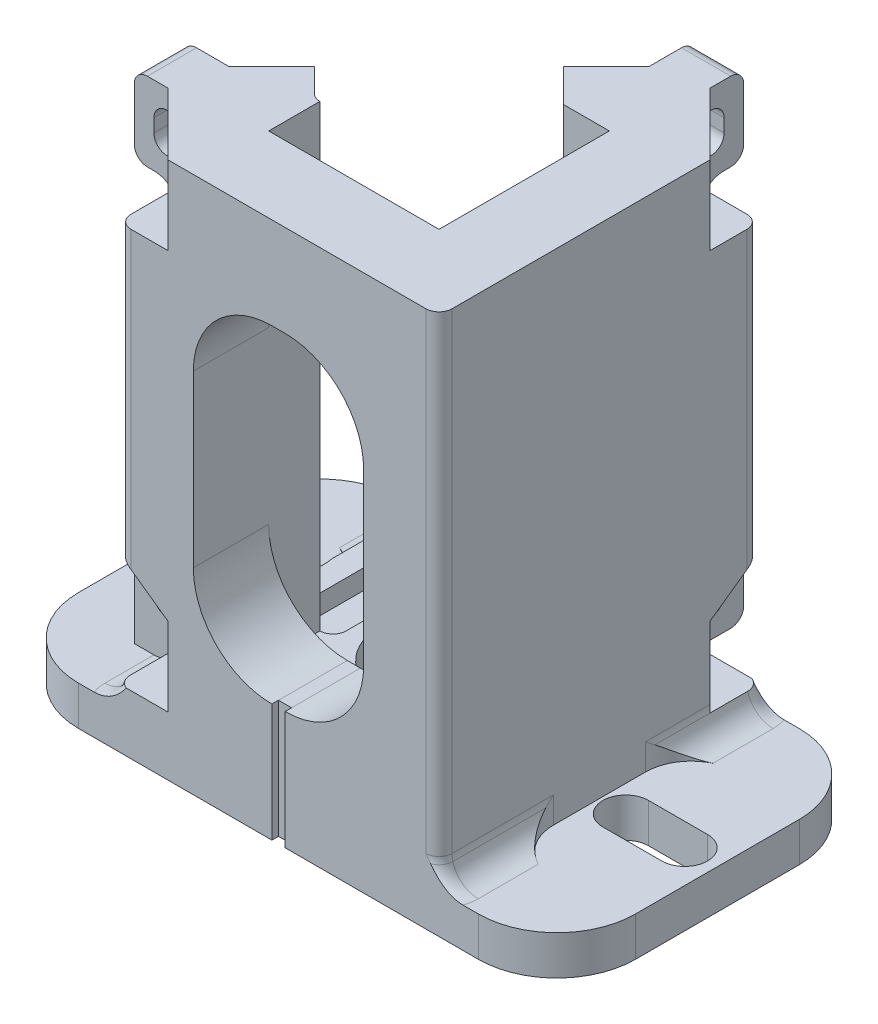
SolidWorks part; units mm, degrees
material "PBT Общее назначение"
ref_plane "Спереди" through (0, 0, 0) normal (0, 0, 1) x (1, 0, 0)
ref_plane "Сверху" through (0, 0, 0) normal (0, 1, 0) x (1, 0, 0)
ref_plane "Справа" through (0, 0, 0) normal (1, 0, 0) x (0, 0, -1)
sketch "Эскиз1" plane through (0, 0, 0) normal (0, 1, 0) x (1, 0, 0)
  line L0 (0, 0) -> (24.5, 0)
  line L1 (0, 0) -> (0, 24.5)
  line L2 (24.5, 0) -> (24.5, 24.5)
  line L3 (0, 24.5) -> (24.5, 24.5)
  dimension "D1" = 24.5
  dimension "D2" = 24.5
extrude "Бобышка-Вытянуть1" add sketch "Эскиз1" along normal blind 38
sketch "Эскиз2" plane through (0, 0, 0) normal (0, -1, 0) x (1, 0, 0)
  line L0 (-9, 0) -> (33.5, 0)
  line L1 (-9, 0) -> (-9, -24.5)
  line L2 (33.5, 0) -> (33.5, -24.5)
  line L4 (-9, -24.5) -> (33.5, -24.5)
  line L5 (0, 0) -> (24.5, 0) construction
  line L6 (24.5, -24.5) -> (0, -24.5) construction
  line L7 (24.5, 0) -> (24.5, -24.5) construction
  line L8 (0, -24.5) -> (0, 0) construction
  dimension "D2" = 9
  dimension "D1" = 9
extrude "Бобышка-Вытянуть2" add sketch "Эскиз2" along normal blind 3
sketch "Эскиз3" plane through (0, 38, 0) normal (0, 1, 0) x (1, 0, 0)
  line L0 (24.5, 12.25) -> (0, 12.25) construction
  line L1 (24.5, 0) -> (24.5, 24.5) construction
  line L2 (0, 24.5) -> (0, 0) construction
  line L3 (12.25, 0) -> (12.25, 24.5) construction
  line L4 (0, 0) -> (24.5, 0) construction
  line L5 (24.5, 24.5) -> (0, 24.5) construction
  line L6 (18.75, 5.75) -> (5.75, 5.75)
  line L7 (18.75, 5.75) -> (18.75, 18.75)
  line L8 (5.75, 5.75) -> (5.75, 18.75)
  line L9 (18.75, 18.75) -> (5.75, 18.75)
  point P12 (5.75, 12.25)
  point P15 (12.25, 5.75)
  dimension "D1" = 13
extrude "Вырез-Вытянуть1" cut sketch "Эскиз3" against normal blind 35
sketch "Эскиз4" plane through (0, 3, 0) normal (0, 1, 0) x (1, 0, 0)
  line L0 (12.25, 5.75) -> (12.25, 18.75) construction
  line L1 (5.75, 5.75) -> (18.75, 5.75) construction
  line L2 (18.75, 18.75) -> (5.75, 18.75) construction
  line L3 (12.25, 12.25) -> (5.75, 12.25) construction
  line L6 (5.75, 18.75) -> (5.75, 5.75) construction
  line L7 (12.25, 12.25) -> (18.75, 12.25) construction
  line L8 (18.75, 5.75) -> (18.75, 18.75) construction
  circle A0 centre (12.25, 12.25) radius 4.5
  dimension "D1" = 9
extrude "Вырез-Вытянуть2" cut sketch "Эскиз4" against normal through all
sketch "Эскиз5" plane through (0, 0, 0) normal (0, 0, 1) x (1, 0, 0)
  line L0 (12.25, 38) -> (12.25, 3) construction
  line L1 (11.75, 31) -> (12.75, 31)
  line L2 (5.75, 25) -> (5.75, 12)
  line L3 (18.75, 25) -> (18.75, 12)
  line L4 (18.75, 38) -> (5.75, 38)
  line L5 (18.75, 3) -> (18.75, 38)
  line L6 (5.75, 3) -> (18.75, 3)
  line L7 (5.75, 38) -> (5.75, 3)
  line L8 (18.75, 38) -> (5.75, 38) construction
  line L9 (18.75, 3) -> (18.75, 38) construction
  line L10 (5.75, 3) -> (18.75, 3) construction
  line L11 (5.75, 38) -> (5.75, 3) construction
  line L12 (11.75, 6) -> (12.75, 6)
  arc A0 (18.75, 12) -> (12.75, 6) centre (12.75, 12) cw
  arc A1 (11.75, 6) -> (5.75, 12) centre (11.75, 12) cw
  arc A2 (18.75, 25) -> (12.75, 31) centre (12.75, 25) ccw
  arc A3 (5.75, 25) -> (11.75, 31) centre (11.75, 25) cw
  point P6 (12.25, 31)
  dimension "D4" = 6
  dimension "D2" = 25
  dimension "D3" = 7
  dimension "D1" = 0
extrude "Вырез-Вытянуть3" cut sketch "Эскиз5" against normal through all
fillet "Скругление1" radius 1 4 edges
sketch "Эскиз7" plane through (0, 38, 0) normal (0, 1, 0) x (1, 0, 0)
  line L0 (0, 12.25) -> (24.5, 12.25) construction
  line L1 (0, 23.5) -> (0, 1) construction
  line L2 (24.5, 1) -> (24.5, 23.5) construction
ref_plane "Плоскость1" through (0, 0, -12.25) normal (0, 0, 1) x (1, 0, 0)
fillet "Скругление2" radius 6 4 edges at (-9, -1.5, -24.5) (33.5, -1.5, -24.5) (-9, -1.5, 0) (33.5, -1.5, 0)
fillet "Скругление3" radius 2 6 edges at (24.2071, 0, -0.2929) (24.2071, 0, -24.2071) (0.2929, 0, -24.2071) (0.2929, 0, -0.2929)
sketch "Эскиз14" plane through (0, 0, 0) normal (0, 1, 0) x (1, 0, 0)
  circle A0 centre (-4.25, 12.25) radius 1.75 construction
  circle A1 centre (-4.25, 12.25) radius 1.75
sketch "Эскиз8" plane through (0, 0, 0) normal (0, 1, 0) x (1, 0, 0)
  line L0 (-9, 12.25) -> (33.5, 12.25) construction
  line L1 (-9, 6) -> (-9, 18.5) construction
  line L2 (33.5, 18.5) -> (33.5, 6) construction
  circle A0 centre (-4, 12.25) radius 1.75
  circle A1 centre (28.5, 12.25) radius 1.75
  dimension "D1" = 5
  dimension "D2" = 3.5
  dimension "D3" = 3.5
  dimension "D4" = 5
extrude "Вырез-Вытянуть4" cut sketch "Эскиз8" against normal through all
sketch "Эскиз9" plane through (0, 38, 0) normal (0, 1, 0) x (1, 0, 0)
  line L0 (12.25, 0) -> (12.25, 24.5) construction
  line L1 (1, 0) -> (23.5, 0) construction
  line L2 (23.5, 24.5) -> (1, 24.5) construction
ref_plane "Плоскость2" through (12.25, 0, 0) normal (1, 0, 0) x (0, 0, -1)
sketch "Эскиз10" plane through (0, 0, 0) normal (0, 1, 0) x (1, 0, 0)
  line L0 (-2, 12.25) -> (-6.5, 12.25) construction
  line L2 (-2, 10.5) -> (-6.5, 10.5)
  line L3 (-2, 14) -> (-6.5, 14)
  circle A1 centre (-4.25, 12.25) radius 1.75 construction
  arc A2 (-2, 10.5) -> (-2, 14) centre (-2, 12.25) ccw
  arc A3 (-6.5, 14) -> (-6.5, 10.5) centre (-6.5, 12.25) ccw
  circle A4 centre (-4.25, 12.25) radius 1.75 construction
  point P4 (-4.25, 12.25)
  dimension "D1" = 4.5
extrude "Вырез-Вытянуть5" cut sketch "Эскиз10" against normal through all
mirror "Зеркальное отражение1" about plane through (12.25, 0, 0) normal (1, 0, 0) of "Вырез-Вытянуть5"
sketch "Эскиз11" plane through (0, 0, 0) normal (0, 0, 1) x (1, 0, 0)
  line L0 (18.75, 38) -> (5.75, 38) construction
  line L1 (18.75, 38) -> (5.75, 38) construction
  line L3 (0, 2) -> (0, 38) construction
  line L4 (1, 38) -> (23.5, 38) construction
  line L5 (3, 38) -> (3, 26.7112) construction
  line L6 (12.25, 38) -> (12.25, 28.1179) construction
  circle A0 centre (3, 33) radius 1
  circle A1 centre (21.5, 33) radius 1
  dimension "D1" = 2
  dimension "D2" = 5
  dimension "D3" = 3
sketch "Эскиз12" plane through (0, 0, 0) normal (0, 1, 0) x (1, 0, 0)
  line L0 (-6.5, 12.25) -> (-3.5, 12.25) construction
  line L1 (32.75, 12.25) -> (28, 12.25) construction
  line L2 (-3.5, 15.75) -> (-3.5, 8.75) construction
  line L3 (0, 15.75) -> (0, 8.75)
  line L4 (-7, 15.75) -> (-7, 8.75)
  line L5 (0, 23.5) -> (0, 1) construction
  line L6 (28, 15.75) -> (28, 8.75) construction
  line L7 (31.5, 15.75) -> (31.5, 8.75)
  line L8 (24.5, 15.75) -> (24.5, 8.75)
  line L9 (24.5, 1) -> (24.5, 23.5) construction
  arc A0 (0, 15.75) -> (-7, 15.75) centre (-3.5, 15.75) ccw
  arc A1 (-7, 8.75) -> (0, 8.75) centre (-3.5, 8.75) ccw
  arc A3 (31.5, 15.75) -> (24.5, 15.75) centre (28, 15.75) ccw
  arc A4 (24.5, 8.75) -> (31.5, 8.75) centre (28, 8.75) ccw
  arc A6 (31, 10.5) -> (31, 14) centre (31, 12.25) ccw construction
  point P3 (-3.5, 12.25)
  point P16 (28, 12.25)
  dimension "D1" = 7
  dimension "D2" = 7
  dimension "D3" = 7
  dimension "D4" = 7
extrude "Вырез-Вытянуть7" cut sketch "Эскиз12" along normal through all
sketch "Эскиз13" plane through (0, 0, 0) normal (0, 0, 1) x (1, 0, 0)
  line L0 (12.25, -3) -> (12.25, 6) construction
  line L1 (27.5, -3) -> (-3, -3) construction
  line L2 (11.75, 6) -> (12.75, 6) construction
  line L3 (11.75, 6) -> (12.75, 6)
  line L4 (11.75, 6) -> (11.75, -3)
  line L5 (12.75, 6) -> (12.75, -3)
  line L6 (11.75, -3) -> (12.75, -3)
  dimension "D1" = 1
extrude "Вырез-Вытянуть8" cut sketch "Эскиз13" against normal blind 0.5
mirror "Зеркальное отражение2" about plane through (0, 0, -12.25) normal (0, 0, 1) of "Вырез-Вытянуть8"
sketch "Эскиз15" plane through (0, 31, 0) normal (0, -1, 0) x (1, 0, 0)
  line L0 (12.25, 0) -> (12.25, -5.75) construction
  line L1 (12.75, 0) -> (11.75, 0) construction
  line L2 (12.75, -5.75) -> (11.75, -5.75) construction
  circle A0 centre (12.25, -2.875) radius 1
  circle A1 centre (12.25, -2.875) radius 1.2
  dimension "D1" = 0.2
  dimension "D2" = 2
ref_plane "Плоскость3" through (0, 0, -23.5) normal (0, 0, -1) x (0, 1, 0)
sketch "Эскиз16" plane through (0, 0, -23.5) normal (0, 0, -1) x (0, 1, 0)
  line L0 (38, 24.5) -> (36.5, 24.5)
  line L1 (38, 24.5) -> (38, 27)
  line L2 (32, 24.5) -> (32, 27)
  line L3 (37, 28) -> (33, 28)
  line L4 (2, 24.5) -> (38, 24.5) construction
  line L5 (36.5, 24.5) -> (36.5, 25.5)
  line L6 (7.5, 24.5) -> (6, 24.5)
  line L7 (35.5, 26.5) -> (34.5, 26.5)
  line L8 (33.5, 24.5) -> (33.5, 25.5)
  line L9 (35, 28) -> (35, 24.5) construction
  line L10 (35, 26.5) -> (35, 24.5) construction
  line L11 (33.5, 24.5) -> (32, 24.5)
  line L12 (7.5, 24.5) -> (7.5, 27)
  line L13 (1.5, 24.5) -> (1.5, 27)
  line L14 (6.5, 28) -> (2.5, 28)
  line L15 (6, 24.5) -> (6, 25.5)
  line L16 (5, 26.5) -> (4, 26.5)
  line L17 (3, 24.5) -> (3, 25.5)
  line L18 (3, 24.5) -> (1.5, 24.5)
  line L19 (4.5, 28) -> (4.5, 24.5) construction
  line L20 (4.5, 26.5) -> (4.5, 24.5) construction
  arc A0 (33.5, 25.5) -> (34.5, 26.5) centre (34.5, 25.5) cw
  arc A1 (35.5, 26.5) -> (36.5, 25.5) centre (35.5, 25.5) cw
  arc A2 (32, 27) -> (33, 28) centre (33, 27) cw
  arc A3 (37, 28) -> (38, 27) centre (37, 27) cw
  arc A4 (3, 25.5) -> (4, 26.5) centre (4, 25.5) cw
  arc A5 (5, 26.5) -> (6, 25.5) centre (5, 25.5) cw
  arc A6 (1.5, 27) -> (2.5, 28) centre (2.5, 27) cw
  arc A7 (6.5, 28) -> (7.5, 27) centre (6.5, 27) cw
  point P16 (33.5, 26.5)
  point P19 (36.5, 26.5)
  point P24 (38, 28)
  dimension "D5" = 1
  dimension "D6" = 1
  dimension "D1" = 6
  dimension "D2" = 3.5
  dimension "D3" = 2
  dimension "D4" = 3
  dimension "D8" = 30.5
  dimension "D7" = 2
sketch "Эскиз17" plane through (0, 38, 0) normal (0, 1, 0) x (1, 0, 0)
  line L4 (23.5, 24.5) -> (1, 24.5)
  line L5 (0, 23.5) -> (0, 1)
  line L6 (1, 0) -> (23.5, 0)
  line L7 (24.5, 1) -> (24.5, 23.5)
  line L8 (23.5, 24.5) -> (1, 24.5)
  line L9 (0, 23.5) -> (0, 1)
  line L10 (1, 0) -> (23.5, 0)
  line L11 (24.5, 1) -> (24.5, 23.5)
  arc A4 (1, 24.5) -> (0, 23.5) centre (1, 23.5) ccw
  arc A5 (0, 1) -> (1, 0) centre (1, 1) ccw
  arc A6 (23.5, 0) -> (24.5, 1) centre (23.5, 1) ccw
  arc A7 (24.5, 23.5) -> (23.5, 24.5) centre (23.5, 23.5) ccw
  arc A8 (1, 24.5) -> (0, 23.5) centre (1, 23.5) ccw
  arc A9 (0, 1) -> (1, 0) centre (1, 1) ccw
  arc A10 (23.5, 0) -> (24.5, 1) centre (23.5, 1) ccw
  arc A11 (24.5, 23.5) -> (23.5, 24.5) centre (23.5, 23.5) ccw
  dimension "D1" = 0
sweep "По траектории1" add profiles "Эскиз16" path "Эскиз17"
sketch "Эскиз18" plane through (0, 38, 0) normal (0, 1, 0) x (1, 0, 0)
  line L0 (5.75, 18.75) -> (1.2242, 23.2758) construction
  line L1 (5.75, 18.75) -> (5.75, 5.75) construction
  line L2 (5.75, 9.2465) -> (-11.9277, 26.9242)
  line L3 (5.75, 9.2465) -> (15.2535, 18.75)
  line L4 (-11.9277, 26.9242) -> (-2.4242, 36.4277)
  line L5 (15.2535, 18.75) -> (-2.4242, 36.4277)
  line L6 (10.5018, 13.9982) -> (-7.1759, 31.6759) construction
  dimension "D1" = 135
  dimension "D2" = 13.44
  dimension "D3" = 25
extrude "Вырез-Вытянуть9" cut sketch "Эскиз18" against normal up to surface (35 mm away) up to face at (12.25, 3, -7.75)
sketch "Эскиз19" plane through (0, 3, 0) normal (0, 1, 0) x (1, 0, 0)
  line L0 (15.2535, 18.75) -> (5.75, 18.75) construction
  line L1 (5.75, 9.2465) -> (5.75, 18.75) construction
  line L2 (16.2535, 17.75) -> (6.75, 17.75)
  line L3 (6.75, 17.75) -> (6.75, 8.2465)
  line L4 (15.2535, 18.75) -> (16.2535, 17.75)
  line L5 (9.5035, 24.5) -> (15.2535, 18.75) construction
  line L6 (5.75, 9.2465) -> (6.75, 8.2465)
  line L7 (5.75, 9.2465) -> (0, 14.9965) construction
  line L8 (11.2535, 22.75) -> (1.75, 22.75)
  line L9 (1.75, 13.2465) -> (1.75, 22.75)
  line L10 (11.2535, 22.75) -> (15.2535, 18.75)
  line L11 (5.75, 9.2465) -> (1.75, 13.2465)
  dimension "D1" = 1
  dimension "D2" = 1
  dimension "D3" = 5
  dimension "D4" = 5
extrude "Вырез-Вытянуть10" cut sketch "Эскиз19" against normal blind 3
sketch "Эскиз21" plane through (0, 3, 0) normal (0, 1, 0) x (1, 0, 0)
  line L0 (-0.0635, 23.5) -> (-0.0635, 16.4137) construction
  line L1 (-0.0635, 23.5) -> (-0.0635, 15.06)
  line L2 (1, 24.5) -> (9.5035, 24.5)
  line L3 (1, 24.5) -> (1, 27)
  line L4 (0.638, 24.5) -> (1, 24.5)
  line L5 (-2.5, 23.5) -> (-0.0635, 23.5)
  line L6 (6.0035, 28) -> (1, 28) construction
  line L7 (0.638, 24.5) -> (1, 24.5)
  line L8 (-3.5, 23.5) -> (-3.5, 18.4965) construction
  line L10 (-1, 15.9965) -> (-3.5, 18.4965) construction
  line L12 (-0.0635, 15.06) -> (-3.5, 18.4965)
  line L13 (6.0035, 28) -> (1, 28)
  line L14 (-3.5, 23.5) -> (-3.5, 18.4965)
  line L15 (6.0035, 28) -> (8.5035, 25.5) construction
  line L16 (6.0035, 28) -> (9.5035, 24.5)
  arc A0 (1, 28) -> (-3.5, 23.5) centre (1, 23.5) ccw construction
  arc A1 (1, 28) -> (-3.5, 23.5) centre (1, 23.5) ccw
  arc A2 (0.638, 24.5) -> (-0.0635, 23.5) centre (1, 23.5) ccw
  arc A3 (1, 27) -> (-2.5, 23.5) centre (1, 23.5) ccw
  arc A4 (0.638, 24.5) -> (-0.0635, 23.5) centre (1, 23.5) ccw
  dimension "D1" = 0
extrude "Вырез-Вытянуть11" cut sketch "Эскиз21" against normal up to surface (1.5 mm away) up to face at (12.25, 1.5, -25.3333)
sketch "Эскиз22" plane through (0, 0, -24.5) normal (0, 0, 1) x (1, 0, 0)
  line L3 (16.7186, 7.5) -> (9.5035, 7.5)
  line L4 (9.5035, 7.5) -> (9.5035, 6.4364)
  line L5 (11.75, 6) -> (12.75, 6)
  line L6 (16.7186, 7.5) -> (9.5035, 7.5)
  line L7 (9.5035, 7.5) -> (9.5035, 6.4364)
  line L8 (11.75, 6) -> (12.75, 6)
  arc A2 (9.5035, 6.4364) -> (11.75, 6) centre (11.75, 12) ccw
  arc A3 (12.75, 6) -> (16.7186, 7.5) centre (12.75, 12) ccw
  arc A4 (9.5035, 6.4364) -> (11.75, 6) centre (11.75, 12) ccw
  arc A5 (12.75, 6) -> (16.7186, 7.5) centre (12.75, 12) ccw
  dimension "D1" = 0
extrude "Вырез-Вытянуть12" cut sketch "Эскиз22" against normal through all
sketch "Эскиз23" plane through (12.75, 0, 0) normal (-1, 0, 0) x (0, 0, 1)
  line L0 (-24.5, 3) -> (-24.5, 6) construction
  line L1 (-24.5, 1.5) -> (-24.5, 7.5)
  line L2 (-28, 2.5) -> (-28, 6.5) construction
  line L3 (-28, 1.5) -> (-28, 7.5)
  line L4 (-27, 7.5) -> (-24.5, 7.5) construction
  line L5 (-28, 7.5) -> (-24.5, 7.5)
  line L6 (-27, 1.5) -> (-24.5, 1.5) construction
  line L7 (-28, 1.5) -> (-24.5, 1.5)
extrude "Вырез-Вытянуть13" cut sketch "Эскиз23" along normal through all and the other way blind 4
ref_plane "Плоскость4" through (0, 0, -8.75) normal (0, 0, -1) x (0, -1, 0)
sketch "Эскиз25" plane through (0, 0, -8.75) normal (0, 0, -1) x (0, -1, 0)
  line L0 (-6.5, 3.5) -> (-2.5, 3.5) construction
  line L1 (-7.5, 3.5) -> (-1.5, 3.5)
  line L3 (-6, 0) -> (-3, 0) construction
  line L4 (-7.5, 0) -> (-7.5, 2.5) construction
  line L5 (-7.5, 0) -> (-7.5, 3.5)
  line L6 (-1.5, 0.0635) -> (-1.5, 2.5) construction
  line L7 (-1.5, 0) -> (-1.5, 3.5)
  line L9 (-7.5, 0) -> (-1.5, 0)
extrude "Вырез-Вытянуть14" cut sketch "Эскиз25" along normal through all
sketch "Эскиз26" plane through (0, 3, 0) normal (0, 1, 0) x (1, 0, 0)
  line L6 (0, 23.862) -> (0, 14.9965)
  line L7 (0, 14.9965) -> (1.75, 13.2465)
  line L8 (1.75, 13.2465) -> (1.75, 22.75)
  line L9 (1.75, 22.75) -> (11.2535, 22.75)
  line L10 (11.2535, 22.75) -> (9.5035, 24.5)
  line L11 (9.5035, 24.5) -> (0.638, 24.5)
  line L12 (0, 23.862) -> (0, 14.9965)
  line L13 (0, 14.9965) -> (1.75, 13.2465)
  line L14 (1.75, 13.2465) -> (1.75, 22.75)
  line L15 (1.75, 22.75) -> (11.2535, 22.75)
  line L16 (11.2535, 22.75) -> (9.5035, 24.5)
  line L17 (9.5035, 24.5) -> (0.638, 24.5)
  arc A1 (0.638, 24.5) -> (0, 23.862) centre (1, 23.5) ccw
  arc A2 (0.638, 24.5) -> (0, 23.862) centre (1, 23.5) ccw
  dimension "D1" = 0
extrude "Вырез-Вытянуть15" cut sketch "Эскиз26" against normal blind 1.5
sketch "Эскиз27" plane through (0, 38, 0) normal (0, 1, 0) x (1, 0, 0)
  line L0 (14.1956, 22.6853) -> (12.6013, 21.091) construction
  line L1 (16.0035, 24.4932) -> (12.7569, 21.2466)
  line L4 (16.0035, 24.4932) -> (16.0035, 28)
  line L5 (6.0035, 28) -> (23.5, 28) construction
  line L6 (6.0035, 28) -> (16.0035, 28)
  line L7 (15.2535, 18.75) -> (7.0035, 27) construction
  line L8 (12.7569, 21.2466) -> (6.0035, 28)
  dimension "D1" = 10
extrude "Вырез-Вытянуть16" cut sketch "Эскиз27" against normal blind 4
sketch "Эскиз29" plane through (0, 34, 0) normal (0, 1, 0) x (1, 0, 0)
  line L2 (9.5035, 24.5) -> (9.5035, 28)
  line L3 (16.0035, 28) -> (6.0035, 28) construction
  line L4 (9.5035, 28) -> (6.0035, 28)
  line L6 (6.0035, 28) -> (7.6375, 26.366) construction
  line L7 (6.0035, 28) -> (9.5035, 24.5)
extrude "Вырез-Вытянуть17" cut sketch "Эскиз29" against normal up to surface (2 mm away) up to face at (15.8768, 32, -25.75)
sketch "Эскиз30" plane through (9.5035, 0, 0) normal (-1, 0, 0) x (0, 0, 1)
  line L5 (-27, 32) -> (-24.5, 32)
  line L6 (-24.5, 32) -> (-24.5, 33.5)
  line L7 (-24.5, 33.5) -> (-25.5, 33.5)
  line L8 (-26.366, 34) -> (-28, 34)
  line L9 (-28, 34) -> (-28, 33)
  line L10 (-27, 32) -> (-24.5, 32)
  line L11 (-24.5, 32) -> (-24.5, 33.5)
  line L12 (-24.5, 33.5) -> (-25.5, 33.5)
  line L13 (-26.366, 34) -> (-28, 34)
  line L14 (-28, 34) -> (-28, 33)
  arc A2 (-26.366, 34) -> (-25.5, 33.5) centre (-25.5, 34.5) ccw
  arc A3 (-28, 33) -> (-27, 32) centre (-27, 33) ccw
  arc A4 (-26.366, 34) -> (-25.5, 33.5) centre (-25.5, 34.5) ccw
  arc A5 (-28, 33) -> (-27, 32) centre (-27, 33) ccw
  dimension "D1" = 0
extrude "Вырез-Вытянуть18" cut sketch "Эскиз30" against normal up to surface (6.5 mm away) up to face at (16.0035, 35.6732, -26.0272)
sketch "Эскиз31" plane through (0, 38, 0) normal (0, 1, 0) x (1, 0, 0)
  line L0 (18.75, 5.75) -> (12.25, 12.25) construction
  line L1 (12.25, 0) -> (12.25, 24.5) construction
  line L2 (5.75, 5.75) -> (18.75, 5.75) construction
  dimension "D1" = 45
ref_plane "Плоскость5" through (12.25, 0, -12.25) normal (0.7071, 0, -0.7071) x (-0.7071, 0, -0.7071)
mirror "Зеркальное отражение5" about plane through (12.25, 0, -12.25) normal (0.7071, 0, -0.7071) of "Вырез-Вытянуть16"
sketch "Эскиз32" plane through (0, 0, -8.4965) normal (0, 0, -1) x (-1, 0, 0)
  line L0 (3.5, 34) -> (3.5, 37) construction
  line L1 (-0.0068, 38) -> (2.5, 38) construction
  line L2 (3.5, 32) -> (3.5, 38)
  line L3 (0, 38) -> (3.5, 38)
  line L4 (2.5, 32) -> (0, 32) construction
  line L5 (3.5, 32) -> (0, 32)
  line L6 (0, 34) -> (0, 36.5) construction
  line L7 (0, 32) -> (0, 38)
extrude "Вырез-Вытянуть19" cut sketch "Эскиз32" along normal up to surface (6.5 mm away) up to face at (1.3157, 22.6281, -13.6808)
sketch "Эскиз33" plane through (0, 1.5, 0) normal (0, -1, 0) x (1, 0, 0)
  line L3 (0.638, 0) -> (1, 0)
  line L4 (1, 0) -> (1, 2.5)
  line L5 (-2.5, -1) -> (-0.0635, -1)
  line L7 (1, 0) -> (1, 3.5)
  line L8 (-3.5, -1) -> (0, -1)
  line L9 (23.5, 2.5) -> (23.5, 0)
  line L10 (23.5, 0) -> (23.862, 0)
  line L11 (24.5635, -1) -> (27, -1)
  line L12 (23.5, 3.5) -> (23.5, 0)
  line L14 (24.5, -1) -> (28, -1)
  line L15 (23.862, -24.5) -> (23.5, -24.5)
  line L16 (23.5, -24.5) -> (23.5, -27)
  line L17 (27, -23.5) -> (24.5635, -23.5)
  line L19 (23.5, -24.5) -> (23.5, -28)
  line L20 (28, -23.5) -> (24.5, -23.5)
  arc A0 (1, 3.5) -> (-3.5, -1) centre (1, -1) ccw construction
  arc A1 (1, 3.5) -> (-3.5, -1) centre (1, -1) ccw
  arc A2 (0.638, 0) -> (-0.0635, -1) centre (1, -1) ccw
  arc A3 (1, 2.5) -> (-2.5, -1) centre (1, -1) ccw
  arc A4 (24.5, -1) -> (23.5, 0) centre (23.5, -1) ccw construction
  arc A5 (23.5, -28) -> (28, -23.5) centre (23.5, -23.5) ccw construction
  arc A6 (23.5, -28) -> (28, -23.5) centre (23.5, -23.5) ccw
  arc A7 (24.5635, -1) -> (23.862, 0) centre (23.5, -1) ccw
  arc A8 (27, -1) -> (23.5, 2.5) centre (23.5, -1) ccw
  arc A9 (23.5, -24.5) -> (24.5, -23.5) centre (23.5, -23.5) ccw construction
  arc A10 (28, -1) -> (23.5, 3.5) centre (23.5, -1) ccw construction
  arc A11 (23.862, -24.5) -> (24.5635, -23.5) centre (23.5, -23.5) ccw
  arc A12 (23.5, -27) -> (27, -23.5) centre (23.5, -23.5) ccw
  arc A14 (28, -1) -> (23.5, 3.5) centre (23.5, -1) ccw
  arc A15 (1, 0) -> (0, -1) centre (1, -1) ccw construction
  arc A16 (1, 0) -> (0, -1) centre (1, -1) ccw
  arc A17 (24.5, -1) -> (23.5, 0) centre (23.5, -1) ccw
  arc A18 (23.5, -24.5) -> (24.5, -23.5) centre (23.5, -23.5) ccw
  dimension "D1" = 0
  dimension "D2" = 0
  dimension "D3" = 0
extrude "Вырез-Вытянуть20" cut sketch "Эскиз33" against normal through all
ref_plane "Плоскость6" through (24, 0, -24) normal (-0.7071, 0, 0.7071) x (0.7071, 0, 0.7071)
sketch "Эскиз35" plane through (24, 0, -24) normal (-0.7071, 0, 0.7071) x (0.7071, 0, 0.7071)
  line L1 (4, 38) -> (-4, 38)
  line L3 (4, 38) -> (4, 32)
  line L4 (-4, 38) -> (-4, 32)
  line L5 (4, 32) -> (-4, 32)
  line L6 (-0.7071, 32) -> (-0.7071, 7.5) construction
  line L7 (0.7071, 7.5) -> (0.7071, 32) construction
  line L8 (-0.7071, 32) -> (-0.7071, 7.5) construction
  line L9 (0.7071, 7.5) -> (0.7071, 32) construction
  line L10 (0.7071, 28) -> (-0.7071, 28) construction
  line L11 (-6.0079, 32) -> (-0.7071, 32) construction
  line L12 (-6.0079, 32) -> (-0.7071, 32) construction
  line L13 (0.7071, 38) -> (2.4749, 38) construction
  line L14 (0.7071, 38) -> (2.4749, 38) construction
  line L15 (0, 28) -> (0, 36.0918) construction
  line L16 (0, 32) -> (0, 38) construction
  line L17 (4, 1.5) -> (-4, 1.5)
  line L18 (4, 7.5) -> (4, 1.5)
  line L19 (4, 7.5) -> (-4, 7.5)
  line L20 (-4, 7.5) -> (-4, 1.5)
  dimension "D1" = 8
  dimension "D2" = 10
  dimension "D4" = 30.5
  dimension "D3" = 2
extrude "Вырез-Вытянуть21" cut sketch "Эскиз35" against normal through all and the other way blind 2
sketch "Эскиз36" plane through (0, 38, 0) normal (0, 1, 0) x (1, 0, 0)
  line L0 (25.4142, 19.7574) -> (28, 19.7574)
  line L1 (28, 1) -> (28, 22.3431) construction
  line L2 (28, 19.7574) -> (28, 22.3431)
  line L3 (25.4142, 19.7574) -> (27, 21.3431) construction
  line L4 (25.4142, 19.7574) -> (28, 22.3431)
  line L5 (19.7574, 25.4142) -> (21.3431, 27) construction
  line L6 (19.7574, 25.4142) -> (22.3431, 28)
  line L7 (16.0035, 28) -> (22.3431, 28) construction
  line L8 (19.7574, 28) -> (22.3431, 28)
  line L9 (19.7574, 25.4142) -> (19.7574, 28)
extrude "Вырез-Вытянуть22" cut sketch "Эскиз36" against normal up to surface (36.5 mm away) up to face at (19.0544, 1.5, -25.6828)
mirror "Зеркальное отражение6" about plane through (12.25, 0, -12.25) normal (0.7071, 0, -0.7071) of "Вырез-Вытянуть21"
mirror "Зеркальное отражение7" about plane through (12.25, 0, -12.25) normal (0.7071, 0, -0.7071) of "Вырез-Вытянуть22"
sketch "Эскиз37" plane through (1.9142, 0, -1.9142) normal (-0.7071, 0, 0.7071) x (0.7071, 0, 0.7071)
  line L0 (0, 38) -> (0, 32) construction
  line L1 (4, 38) -> (-4, 38) construction
  line L2 (-2.7071, 32) -> (2.7071, 32) construction
  line L3 (-0.0449, 1.5) -> (-0.0449, 7.5) construction
  line L8 (-2.7969, 1.5) -> (2.7071, 1.5) construction
  line L9 (2.7071, 7.5) -> (-2.7071, 7.5) construction
  circle A0 centre (-0.0449, 4.5) radius 1.1
  circle A1 centre (0, 35) radius 1.1
  dimension "D1" = 2.2
  dimension "D2" = 2.2
extrude "Вырез-Вытянуть23" cut sketch "Эскиз37" against normal through all
sketch "Эскиз38" plane through (0, 0, -1) normal (0, 0, 1) x (1, 0, 0)
  line L8 (28, 33) -> (28, 37)
  line L9 (27, 38) -> (24.5, 38)
  line L10 (24.5, 38) -> (24.5, 36.5)
  line L11 (24.5, 36.5) -> (25.5, 36.5)
  line L12 (26.5, 35.5) -> (26.5, 34.5)
  line L13 (25.5, 33.5) -> (24.5, 33.5)
  line L14 (24.5, 33.5) -> (24.5, 32)
  line L15 (24.5, 32) -> (27, 32)
  line L16 (28, 33) -> (28, 37)
  line L17 (27, 38) -> (24.5, 38)
  line L18 (24.5, 38) -> (24.5, 36.5)
  line L19 (24.5, 36.5) -> (25.5, 36.5)
  line L20 (26.5, 35.5) -> (26.5, 34.5)
  line L21 (25.5, 33.5) -> (24.5, 33.5)
  line L22 (24.5, 33.5) -> (24.5, 32)
  line L23 (24.5, 32) -> (27, 32)
  line L25 (24.5, 6) -> (25.5, 6)
  line L26 (26.5, 5) -> (26.5, 4)
  line L27 (25.5, 3) -> (24.5, 3)
  line L28 (24.5, 3) -> (24.5, 1.5)
  line L29 (24.5, 1.5) -> (24.5635, 1.5)
  line L30 (24.5635, 1.5) -> (27, 1.5)
  line L31 (28, 2.5) -> (28, 6.5)
  line L32 (27, 7.5) -> (24.5, 7.5)
  line L33 (24.5, 7.5) -> (24.5, 6)
  line L34 (24.5, 6) -> (25.5, 6)
  line L35 (26.5, 5) -> (26.5, 4)
  line L36 (25.5, 3) -> (24.5, 3)
  line L37 (24.5, 3) -> (24.5, 1.5)
  line L38 (24.5, 1.5) -> (24.5635, 1.5)
  line L39 (24.5635, 1.5) -> (27, 1.5)
  line L40 (28, 2.5) -> (28, 6.5)
  line L41 (27, 7.5) -> (24.5, 7.5)
  line L42 (24.5, 7.5) -> (24.5, 6)
  arc A4 (28, 37) -> (27, 38) centre (27, 37) ccw
  arc A5 (26.5, 35.5) -> (25.5, 36.5) centre (25.5, 35.5) ccw
  arc A6 (25.5, 33.5) -> (26.5, 34.5) centre (25.5, 34.5) ccw
  arc A7 (27, 32) -> (28, 33) centre (27, 33) ccw
  arc A8 (28, 37) -> (27, 38) centre (27, 37) ccw
  arc A9 (26.5, 35.5) -> (25.5, 36.5) centre (25.5, 35.5) ccw
  arc A10 (25.5, 33.5) -> (26.5, 34.5) centre (25.5, 34.5) ccw
  arc A11 (27, 32) -> (28, 33) centre (27, 33) ccw
  arc A12 (26.5, 5) -> (25.5, 6) centre (25.5, 5) ccw
  arc A13 (25.5, 3) -> (26.5, 4) centre (25.5, 4) ccw
  arc A14 (27, 1.5) -> (28, 2.5) centre (27, 2.5) ccw
  arc A15 (28, 6.5) -> (27, 7.5) centre (27, 6.5) ccw
  arc A16 (26.5, 5) -> (25.5, 6) centre (25.5, 5) ccw
  arc A17 (25.5, 3) -> (26.5, 4) centre (25.5, 4) ccw
  arc A18 (27, 1.5) -> (28, 2.5) centre (27, 2.5) ccw
  arc A19 (28, 6.5) -> (27, 7.5) centre (27, 6.5) ccw
  dimension "D1" = 0
  dimension "D2" = 0
extrude "Вырез-Вытянуть24" cut sketch "Эскиз38" against normal through all
sketch "Эскиз39" plane through (23.5, 0, 0) normal (1, 0, 0) x (0, 0, -1)
  line L8 (-2.5, 32) -> (0, 32)
  line L9 (0, 32) -> (0, 33.5)
  line L10 (0, 33.5) -> (-1, 33.5)
  line L11 (-2, 34.5) -> (-2, 35.5)
  line L12 (-1, 36.5) -> (0, 36.5)
  line L13 (0, 36.5) -> (0, 38)
  line L14 (0, 38) -> (-2.5, 38)
  line L15 (-3.5, 37) -> (-3.5, 33)
  line L16 (-2.5, 32) -> (0, 32)
  line L17 (0, 32) -> (0, 33.5)
  line L18 (0, 33.5) -> (-1, 33.5)
  line L19 (-2, 34.5) -> (-2, 35.5)
  line L20 (-1, 36.5) -> (0, 36.5)
  line L21 (0, 36.5) -> (0, 38)
  line L22 (0, 38) -> (-2.5, 38)
  line L23 (-3.5, 37) -> (-3.5, 33)
  line L24 (0, 6) -> (0, 7.5)
  line L25 (0, 7.5) -> (-2.5, 7.5)
  line L26 (-3.5, 6.5) -> (-3.5, 2.5)
  line L27 (-2.5, 1.5) -> (0, 1.5)
  line L28 (0, 1.5) -> (0, 3)
  line L29 (0, 3) -> (-1, 3)
  line L30 (-2, 4) -> (-2, 5)
  line L31 (-1, 6) -> (0, 6)
  line L32 (0, 6) -> (0, 7.5)
  line L33 (0, 7.5) -> (-2.5, 7.5)
  line L34 (-3.5, 6.5) -> (-3.5, 2.5)
  line L35 (-2.5, 1.5) -> (0, 1.5)
  line L36 (0, 1.5) -> (0, 3)
  line L37 (0, 3) -> (-1, 3)
  line L38 (-2, 4) -> (-2, 5)
  line L39 (-1, 6) -> (0, 6)
  arc A4 (-2, 34.5) -> (-1, 33.5) centre (-1, 34.5) ccw
  arc A5 (-1, 36.5) -> (-2, 35.5) centre (-1, 35.5) ccw
  arc A6 (-2.5, 38) -> (-3.5, 37) centre (-2.5, 37) ccw
  arc A7 (-3.5, 33) -> (-2.5, 32) centre (-2.5, 33) ccw
  arc A8 (-2, 34.5) -> (-1, 33.5) centre (-1, 34.5) ccw
  arc A9 (-1, 36.5) -> (-2, 35.5) centre (-1, 35.5) ccw
  arc A10 (-2.5, 38) -> (-3.5, 37) centre (-2.5, 37) ccw
  arc A11 (-3.5, 33) -> (-2.5, 32) centre (-2.5, 33) ccw
  arc A12 (-2.5, 7.5) -> (-3.5, 6.5) centre (-2.5, 6.5) ccw
  arc A13 (-3.5, 2.5) -> (-2.5, 1.5) centre (-2.5, 2.5) ccw
  arc A14 (-2, 4) -> (-1, 3) centre (-1, 4) ccw
  arc A15 (-1, 6) -> (-2, 5) centre (-1, 5) ccw
  arc A16 (-2.5, 7.5) -> (-3.5, 6.5) centre (-2.5, 6.5) ccw
  arc A17 (-3.5, 2.5) -> (-2.5, 1.5) centre (-2.5, 2.5) ccw
  arc A18 (-2, 4) -> (-1, 3) centre (-1, 4) ccw
  arc A19 (-1, 6) -> (-2, 5) centre (-1, 5) ccw
  dimension "D1" = 0
  dimension "D2" = 0
extrude "Вырез-Вытянуть25" cut sketch "Эскиз39" against normal through all
ref_plane "Плоскость7" through (1.9142, 0, 1.9142) normal (0.7071, 0, 0.7071) x (0.7071, 0, -0.7071)
sketch "Эскиз40" plane through (1.9142, 0, 1.9142) normal (0.7071, 0, 0.7071) x (0.7071, 0, -0.7071)
  line L0 (0.4142, 32) -> (0.4142, 7.5) construction
  line L1 (0.4142, 9.7929) -> (0.4142, 7.5)
  line L2 (0.7071, 7.5) -> (2.7071, 7.5) construction
  line L3 (0.4142, 7.5) -> (2.7071, 7.5)
  line L4 (2.7071, 7.5) -> (0.4142, 9.7929)
  line L5 (34.234, 7.5) -> (34.234, 32) construction
  line L6 (34.234, 7.5) -> (34.234, 9.7929)
  line L7 (33.9411, 7.5) -> (31.9411, 7.5) construction
  line L8 (34.234, 7.5) -> (31.9411, 7.5)
  line L9 (31.9411, 7.5) -> (34.234, 9.7929)
  dimension "D1" = 45
  dimension "D2" = 45
extrude "Вырез-Вытянуть26" cut sketch "Эскиз40" against normal through all
fillet "Скругление4" radius 1 4 edges at (1.75, 0.75, -22.75) (6.75, 1.5, -17.75) (6.75, 1.5, -8.2465) (16.2535, 1.5, -17.75)
fillet "Скругление5" radius 2 2 edges at (0, 32, -6.1625) (18.3375, 32, -24.5)
sketch "Эскиз41" plane through (0, 0, -8.75) normal (0, 0, -1) x (-1, 0, 0)
  line L0 (0, 3) -> (1, 3) construction
  line L1 (0, 3) -> (3.5, 3)
  line L2 (3.5, 2.5) -> (3.5, 6.5) construction
  line L3 (0, 3) -> (0, 1.5) construction
  line L4 (0, 3) -> (0, 0)
  line L5 (6.5, 0) -> (2, 0) construction
  line L6 (3.5, 0) -> (0, 0)
  line L7 (3.5, 0) -> (3.5, 3)
extrude "Бобышка-Вытянуть3" add sketch "Эскиз41" against normal up to surface (4.0074 mm away) up to face at (-1.8738, 4.5, -4.7426)
sketch "Эскиз42" plane through (0, 1.5, 0) normal (0, -1, 0) x (1, 0, 0)
  line L3 (-0.0635, -3.8919) -> (-0.9142, -4.7426)
  line L4 (-0.9142, -4.7426) -> (-0.0635, -4.7426)
  line L5 (-0.0635, -4.7426) -> (-0.0635, -3.8919)
  line L6 (-0.0635, -3.8919) -> (-0.9142, -4.7426)
  line L7 (-0.9142, -4.7426) -> (-0.0635, -4.7426)
  line L8 (-0.0635, -4.7426) -> (-0.0635, -3.8919)
  dimension "D1" = 0
extrude "Вырез-Вытянуть27" cut sketch "Эскиз42" against normal up to surface (6 mm away) up to face at (-1.1828, 7.5, -6.1627)
fillet "Скругление6" radius 2 2 edges at (24.2071, 1.5, -0.2929) (24.5, 1.5, -18.2108)
